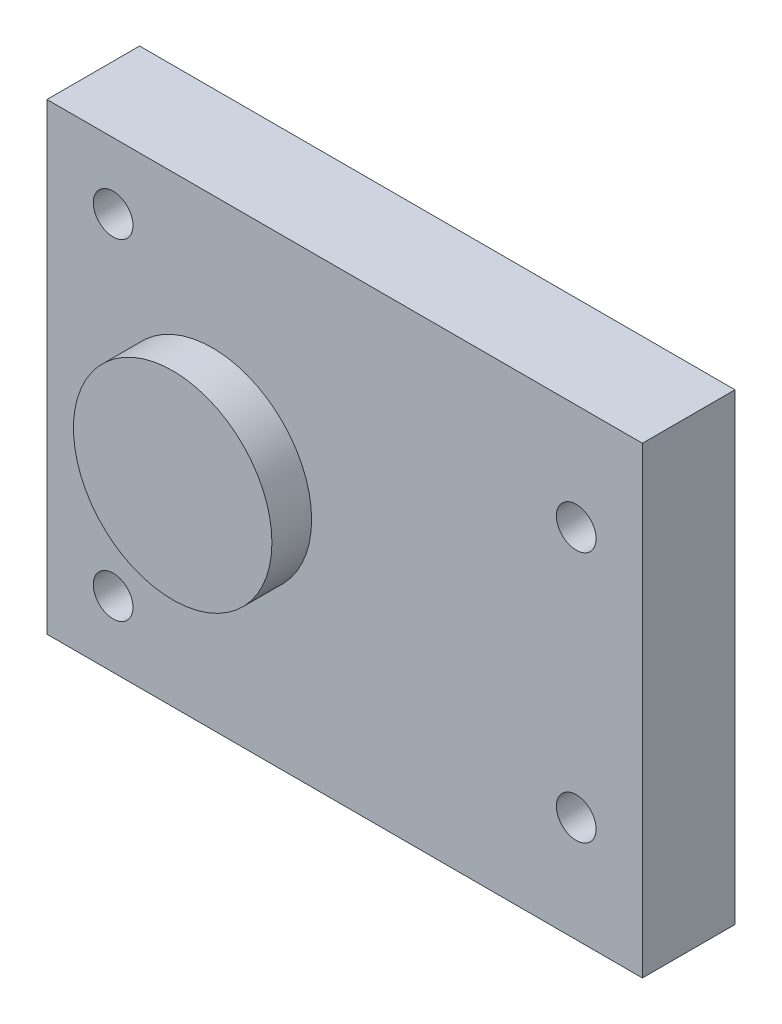
SolidWorks part; units mm, degrees
ref_plane "Front Plane" through (0, 0, 0) normal (0, 0, 1) x (1, 0, 0)
ref_plane "Top Plane" through (0, 0, 0) normal (0, 1, 0) x (1, 0, 0)
ref_plane "Right Plane" through (0, 0, 0) normal (1, 0, 0) x (0, 0, -1)
sketch "Sketch1" plane through (0, 0, 0) normal (0, 0, 1) x (1, 0, 0)
  line L1 (-92.5, 17.5) -> (-47.5, 17.5)
  line L2 (-92.5, 17.5) -> (-92.5, -17.5)
  line L3 (-92.5, -17.5) -> (-47.5, -17.5)
  line L4 (-47.5, 17.5) -> (-47.5, -17.5)
  line L5 (-92.5, 0) -> (-56.7435, 0) construction
  circle A0 centre (-87.5, 12.5) radius 1.5
  circle A1 centre (-87.5, -12.5) radius 1.5
  circle A2 centre (-52.5, 9.5) radius 1.5
  circle A3 centre (-52.5, -9.5) radius 1.5
  circle A4 centre (-80, 0) radius 4
  dimension "D2" = 3
  dimension "D5" = 8
  dimension "D1" = 45
  dimension "D3" = 5
  dimension "D4" = 5
extrude "Boss-Extrude1" add sketch "Sketch1" along normal blind 7 contours L4 L1 L2 A4 L3 A3 A2 A0 A1 | L5 A4 | A4 L5 region at (-80, 1.6977, 0) region at (-80, -1.6977, 0) region at (-70, 16.9299, 0)
sketch "Sketch2" plane through (-47.5, 0, 0) normal (1, 0, 0) x (0, 0, -1)
  line L1 (0, 25) -> (-7, 25)
  line L2 (0, 25) -> (0, -25)
  line L3 (0, -25) -> (-7, -25)
  line L4 (-7, 25) -> (-7, -25)
  line L6 (-7, 17.5) -> (0, 17.5) construction
  line L7 (-7, -17.5) -> (0, -17.5) construction
  line L8 (-7, 17.5) -> (-7, -17.5) construction
  dimension "D2" = 7.5
  dimension "D3" = 7.5
sketch "Sketch5" plane through (0, 0, 7) normal (0, 0, 1) x (1, 0, 0)
  circle A0 centre (-80, 0) radius 7.5
  dimension "D1" = 15
extrude "Boss-Extrude5" add sketch "Sketch5" along normal blind 3
extrude "Cut-Extrude1" cut sketch "Sketch1<3>" along normal blind 3 and the other way blind 3 contours L5 A4 | A4 L5 region at (-80, 1.6977, 0) region at (-80, -1.6977, 0)
sketch "Sketch1<3>" plane through (0, 0, 0) normal (0, 0, 1) x (1, 0, 0) same geometry as "Sketch1"
